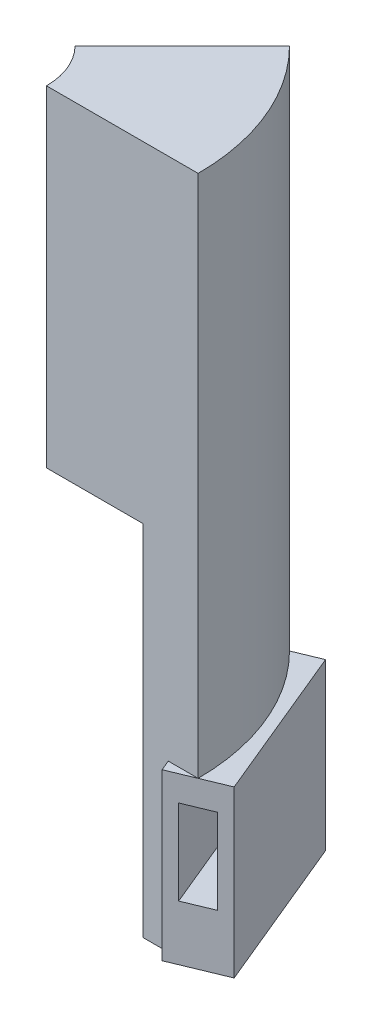
SolidWorks part; units mm, degrees
ref_plane "Front Plane" through (0, 0, 0) normal (0, 0, 1) x (1, 0, 0)
ref_plane "Top Plane" through (0, 0, 0) normal (0, 1, 0) x (1, 0, 0)
ref_plane "Right Plane" through (0, 0, 0) normal (1, 0, 0) x (0, 0, -1)
sketch "Sketch1" plane through (0, 0, 0) normal (0, 0, 1) x (1, 0, 0)
  line L0 (0, 0) -> (0, 60)
  line L1 (0, 60) -> (27.5, 60)
  line L2 (27.5, 60) -> (27.5, -65)
  line L3 (27.5, -65) -> (17.5, -65)
  line L4 (17.5, -65) -> (17.5, 0)
  line L5 (17.5, 0) -> (0, 0)
  line L6 (-12.5, 0) -> (-12.5, 41.9322) construction
  dimension "D1" = 60
  dimension "D2" = 65
  dimension "D3" = 17.5
  dimension "D4" = 10
  dimension "D5" = 12.5
revolve "Revolve1" add sketch "Sketch1" angle 45 about L6
ref_plane "Plane1" through (23.4727, 0, -9.7227) normal (-0.9239, 0, 0.3827) x (0.3827, 0, 0.9239)
sketch "Sketch2" plane through (23.4727, 0, -9.7227) normal (-0.9239, 0, 0.3827) x (0.3827, 0, 0.9239)
  line L0 (-20.0909, -65) -> (-20.0909, 60) construction
  line L1 (10.5238, -65) -> (-20.0909, -65)
  line L2 (10.5238, -65) -> (10.5238, -35)
  line L3 (10.5238, -35) -> (-20.0909, -35)
  line L4 (-20.0909, -65) -> (-20.0909, -35)
  point P7 (-20.0909, -40.9481)
  dimension "D1" = 30
extrude "Boss-Extrude1" add sketch "Sketch2" against normal mid plane 10
sketch "Sketch3" plane through (4.0273, 0, 9.7227) normal (0.3827, 0, 0.9239) x (0.9239, 0, -0.3827)
  line L0 (25.4067, -65) -> (25.4067, -42.9465) construction
  line L1 (30.4067, -65) -> (20.4067, -65) construction
  line L3 (22.7067, -39.6) -> (28.1067, -39.6)
  line L4 (22.7067, -39.6) -> (22.7067, -55)
  line L5 (22.7067, -55) -> (28.1067, -55)
  line L6 (28.1067, -39.6) -> (28.1067, -55)
  line L7 (22.7067, -39.6) -> (28.1067, -55) construction
  line L8 (22.7067, -55) -> (28.1067, -39.6) construction
  point P4 (25.4067, -47.3)
  dimension "D1" = 10
  dimension "D3" = 5.4
  dimension "D4" = 15.4
extrude "Cut-Extrude1" cut sketch "Sketch3" against normal through all
